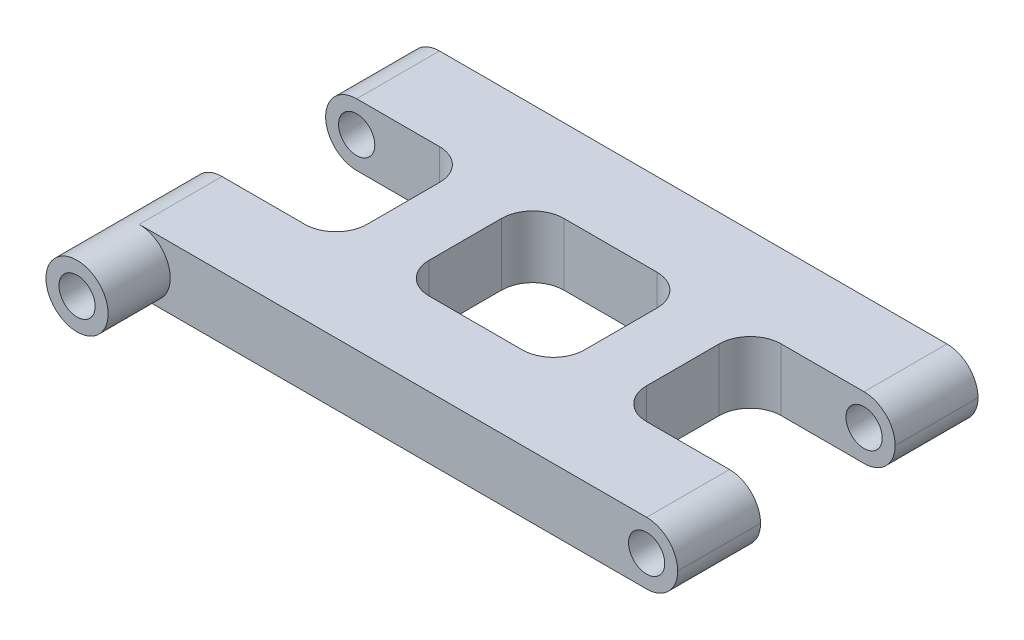
SolidWorks part; units mm, degrees
ref_plane "Alzado" through (0, 0, 0) normal (0, 0, 1) x (1, 0, 0)
ref_plane "Planta" through (0, 0, 0) normal (0, 1, 0) x (1, 0, 0)
ref_plane "Vista lateral" through (0, 0, 0) normal (1, 0, 0) x (0, 0, -1)
sketch "Croquis1" plane through (0, 0, 0) normal (0, 1, 0) x (1, 0, 0)
  line L0 (0, 0) -> (0, 8)
  line L1 (0, 8) -> (14, 8)
  line L2 (14, 8) -> (14, 21)
  line L3 (14, 21) -> (0, 21)
  line L4 (0, 21) -> (0, 29)
  line L16 (0, 29) -> (55, 29)
  line L17 (55, 29) -> (55, 21)
  line L18 (14, 14.5) -> (48, 14.5) construction
  line L22 (55, 0) -> (55, 8)
  line L23 (55, 8) -> (41, 8)
  line L24 (55, 21) -> (41, 21)
  line L25 (41, 21) -> (41, 8)
  line L26 (0, 0) -> (55, 0)
  line L27 (20, 8) -> (35, 8)
  line L28 (20, 8) -> (20, 21)
  line L29 (20, 21) -> (35, 21)
  line L30 (35, 8) -> (35, 21)
  dimension "D1" = 8
  dimension "D2" = 13
  dimension "D3" = 8
  dimension "D4" = 55
  dimension "D5" = 8
  dimension "D6" = 14
  dimension "D7" = 15
  dimension "D8" = 55
  dimension "D9" = 14
  dimension "D10" = 8
  dimension "D11" = 13
  dimension "D12" = 6
  dimension "D13" = 6
extrude "Saliente-Extruir1" add sketch "Croquis1" along normal mid plane 6
fillet "Redondeo1" radius 3 8 edges at (0, -3, -4) (0, 3, -4) (0, -3, -25) (0, 3, -25) (55, -3, -4) (55, 3, -4) (55, 3, -25) (55, -3, -25)
sketch "Croquis6" plane through (0, 0, 0) normal (0, 0, 1) x (1, 0, 0)
  circle A0 centre (3, 0) radius 3
  dimension "D1" = 6
extrude "Saliente-Extruir2" add sketch "Croquis6" along normal blind 6
sketch "Croquis2" plane through (0, 0, 6) normal (0, 0, 1) x (1, 0, 0)
  circle A0 centre (3, 0) radius 1.75
  dimension "D1" = 3.5
extrude "Cortar-Extruir1" cut sketch "Croquis2" against normal through all both and the other way through all
sketch "Croquis3" plane through (0, 0, 0) normal (0, 0, 1) x (1, 0, 0)
  line L1 (3, -3) -> (52, -3) construction
  circle A0 centre (52, 0) radius 1.75
  dimension "D1" = 3.5
  dimension "D2" = 3
  dimension "D3" = 3
extrude "Cortar-Extruir2" cut sketch "Croquis3" against normal through all both
fillet "Redondeo2" radius 3 8 edges at (14, 0, -8) (35, 0, -8) (20, 0, -8) (41, 0, -8) (41, 0, -21) (20, 0, -21) (14, 0, -21) (35, 0, -21)
